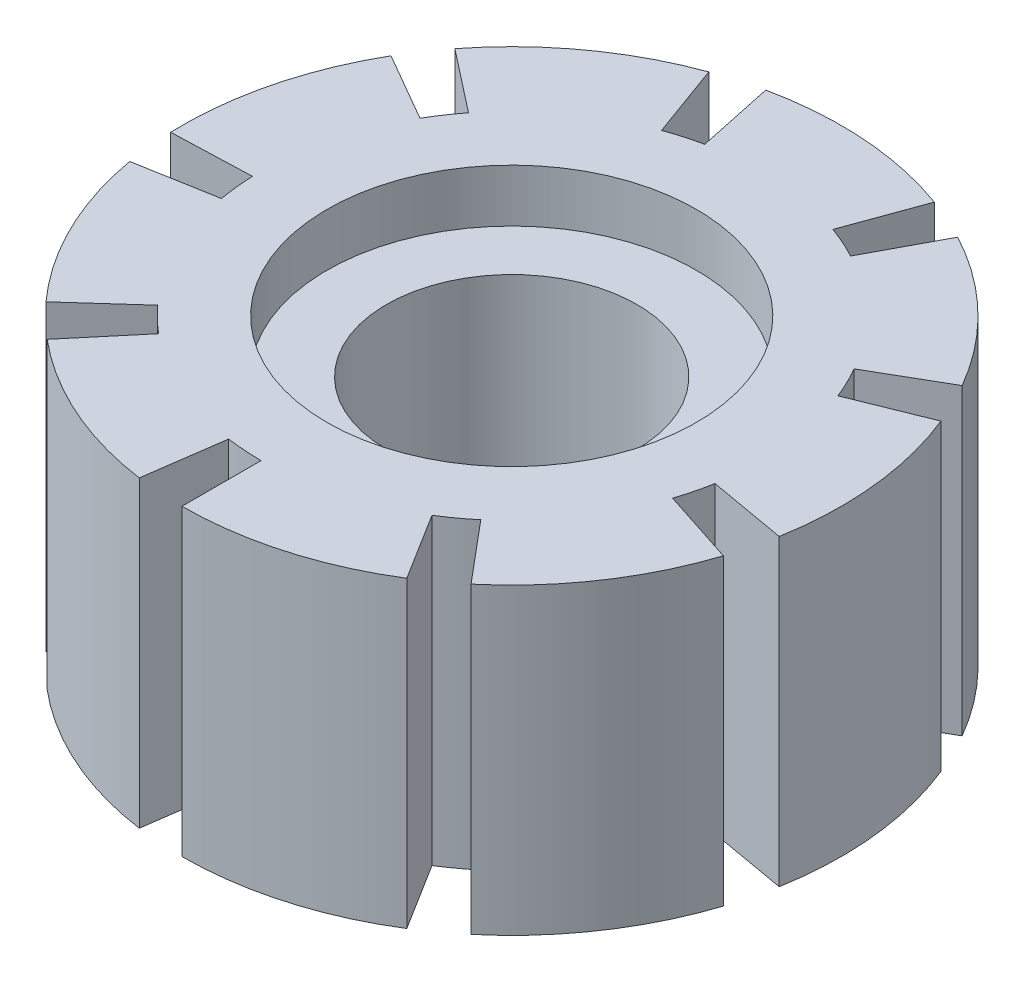
SolidWorks part; units mm, degrees
ref_plane "Front Plane" through (0, 0, 0) normal (0, 0, 1) x (1, 0, 0)
ref_plane "Top Plane" through (0, 0, 0) normal (0, 1, 0) x (1, 0, 0)
ref_plane "Right Plane" through (0, 0, 0) normal (1, 0, 0) x (0, 0, -1)
sketch "Sketch1" plane through (0, 0, 0) normal (0, 1, 0) x (1, 0, 0)
  circle A0 centre (0, 0) radius 9.5
  circle A1 centre (0, 0) radius 25
  dimension "D1" = 19
  dimension "D2" = 50
extrude "Boss-Extrude1" add sketch "Sketch1" along normal blind 15
sketch "Sketch4" plane through (0, 0, 0) normal (0, 0, 1) x (1, 0, 0)
  line L0 (-25, 7.5) -> (29.7231, 7.5) construction
  line L1 (-25, 15) -> (-25, 0) construction
sketch "Sketch2" plane through (0, 15, 0) normal (0, 1, 0) x (1, 0, 0)
  circle A0 centre (0, 0) radius 14
  circle A1 centre (0, 0) radius 25
  dimension "D1" = 28
extrude "Boss-Extrude2" add sketch "Sketch2" along normal blind 4
ref_plane "Plane1" through (0, 7.5, 0) normal (0, 1, 0) x (1, 0, 0)
mirror "Mirror1" about plane through (0, 7.5, 0) normal (0, 1, 0) of "Boss-Extrude2"
sketch "Sketch6" plane through (0, -4, 0) normal (0, -1, 0) x (1, 0, 0)
  line L0 (-3.4793, 24.7567) -> (-2.6443, 18.8151)
  line L1 (0, 19) -> (0, 25)
  arc A0 (-3.4793, 24.7567) -> (0, 25) centre (0, 0) cw
  circle A1 centre (0, 0) radius 25 construction
  arc A2 (-2.6443, 18.8151) -> (0, 19) centre (0, 0) cw
  dimension "D3" = 19
  dimension "D1" = 8
  dimension "D2" = 6
extrude "Cut-Extrude1" cut sketch "Sketch6" against normal through all
pattern_circular "CirPattern1" count 9 over 360 about axis through (0, 15, 0) along (0, -1, 0) of "Cut-Extrude1"
